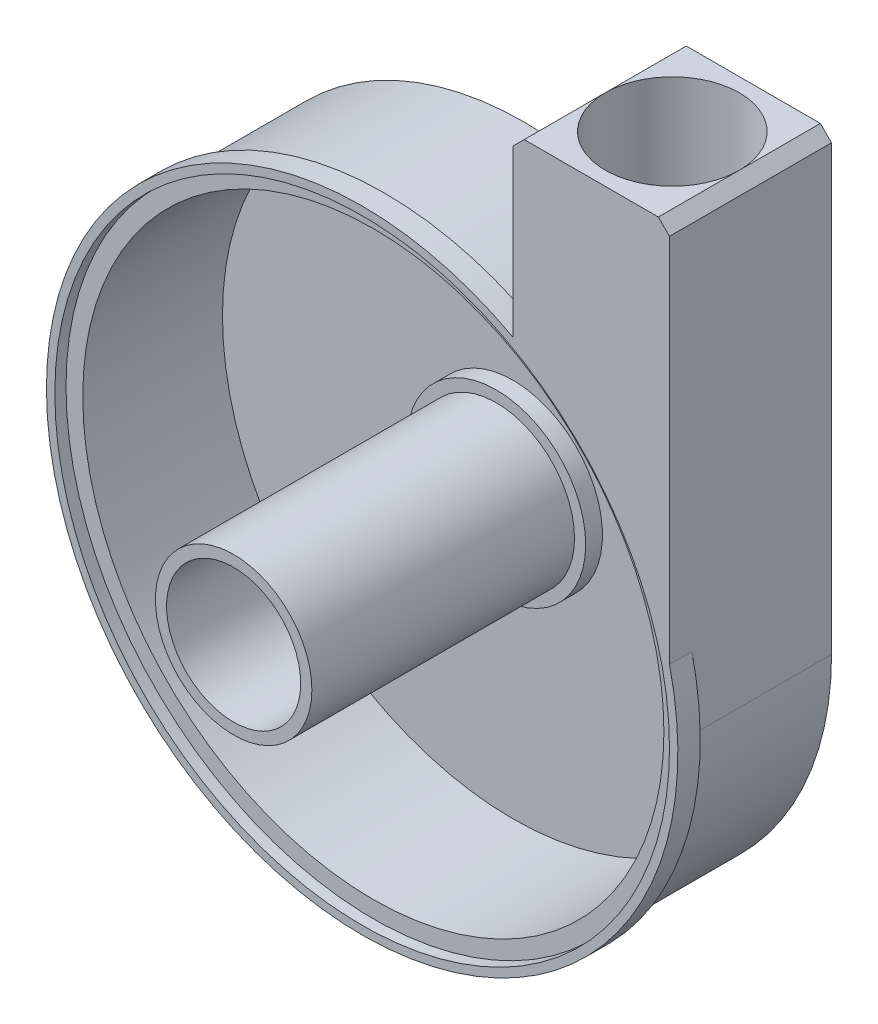
SolidWorks part; units mm, degrees
ref_plane "Front Plane" through (0, 0, 0) normal (0, 0, 1) x (1, 0, 0)
ref_plane "Top Plane" through (0, 0, 0) normal (0, 1, 0) x (1, 0, 0)
ref_plane "Right Plane" through (0, 0, 0) normal (1, 0, 0) x (0, 0, -1)
sketch "Sketch1" plane through (0, 0, 0) normal (0, 0, 1) x (1, 0, 0)
  circle A0 centre (0, 0) radius 55
  circle A1 centre (0, 0) radius 52
extrude "Boss-Extrude1" add sketch "Sketch1" along normal blind 25
sketch "Sketch2" plane through (0, 0, 25) normal (0, 0, 1) x (1, 0, 0)
  line L0 (27, 81.2871) -> (27, 47.9166)
  line L1 (55, 0) -> (55, 81.2871)
  line L2 (55, 81.2871) -> (27, 81.2871)
  circle A3 centre (0, 0) radius 55 construction
  arc A4 (55, 0) -> (27, 47.9166) centre (0, 0) ccw
  circle A5 centre (0, 0) radius 55
  arc A6 (27, 47.9166) -> (55, 0) centre (0, 0) ccw
  circle M6 centre (0, 0) radius 55
  dimension "D1" = 0
extrude "Boss-Extrude2" add sketch "Sketch2" against normal blind 29 from offset 2 contours L2 L1 M6 region at (42.8095, 56.3824, 25)
sketch "Sketch5" plane through (0, 0, 0) normal (0, 0, -1) x (-1, 0, 0)
  circle A0 centre (0, 0) radius 55
  circle A1 centre (0, 0) radius 12
extrude "Boss-Extrude3" add sketch "Sketch5" along normal blind 2
sketch "Sketch6" plane through (0, 0, 0) normal (0, 0, 1) x (1, 0, 0)
  circle A0 centre (0, 0) radius 12
  circle A1 centre (0, 0) radius 14
extrude "Boss-Extrude4" add sketch "Sketch6" along normal blind 50
sketch "Sketch7" plane through (0, 0, 0) normal (0, 0, 1) x (1, 0, 0)
  circle A0 centre (0, 0) radius 16
  circle A1 centre (0, 0) radius 14
extrude "Boss-Extrude5" add sketch "Sketch7" along normal blind 3
sketch "Sketch8" plane through (0, 0, 25) normal (0, 0, 1) x (1, 0, 0)
  circle A0 centre (0, 0) radius 52
  circle A1 centre (0, 0) radius 55
extrude "Boss-Extrude6" add sketch "Sketch8" against normal blind 2
sketch "Sketch9" plane through (0, 81.2871, 0) normal (0, 1, 0) x (1, 0, 0)
  circle A0 centre (41, -12.5) radius 12
extrude "Cut-Extrude1" cut sketch "Sketch9" against normal blind 80
chamfer "Chamfer1" distance 2 angle 45 2 edges at (27, 81.2871, 12.5) (55, 81.2871, 12.5)
sketch "Sketch11" plane through (0, 0, 25) normal (0, 0, 1) x (1, 0, 0)
  circle A0 centre (0, 0) radius 55
  circle A1 centre (0, 0) radius 56.5
extrude "Boss-Extrude8" add sketch "Sketch11" along normal blind 4 from offset 2 offset against normal yes
